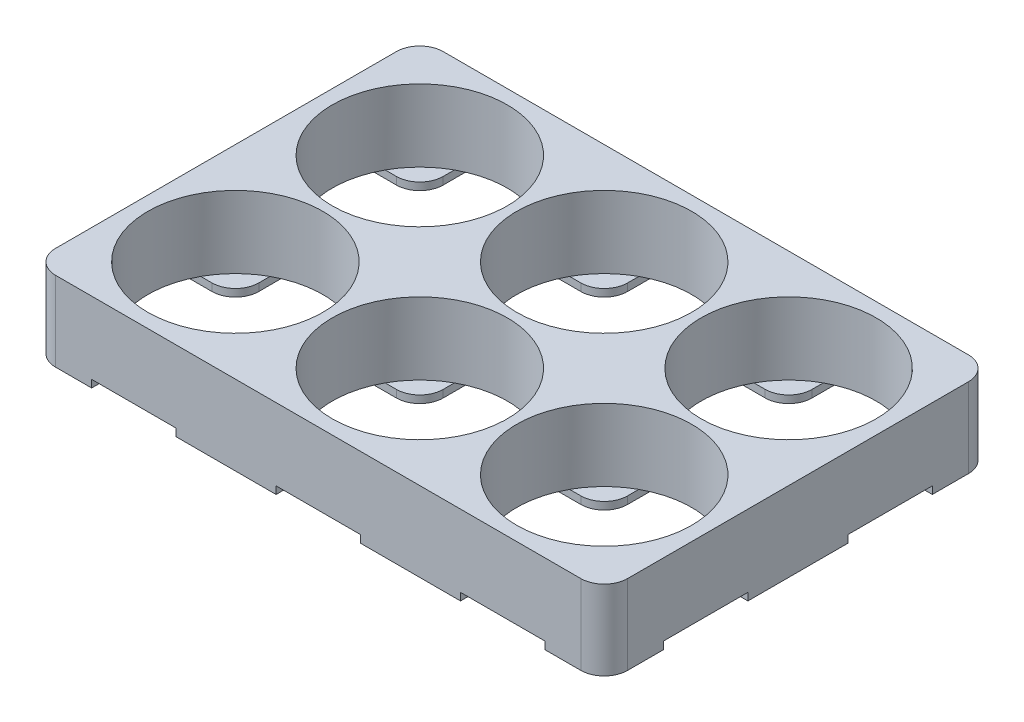
SolidWorks part; units mm, degrees
note: The reader was unsure of these and kept them because the rebuilt part matched: shared geometry of "Sketch5<3>", "Sketch12<3>".
ref_plane "Front Plane" through (0, 0, 0) normal (0, 0, 1) x (1, 0, 0)
ref_plane "Top Plane" through (0, 0, 0) normal (0, 1, 0) x (1, 0, 0)
ref_plane "Right Plane" through (0, 0, 0) normal (1, 0, 0) x (0, 0, -1)
sketch "Sketch3" plane through (0, 0, 0) normal (0, 1, 0) x (1, 0, 0)
  line L0 (-19.7, 9.85) -> (-10.35, 9.85) construction
  line L1 (-10.35, 9.85) -> (-9.35, 9.85) construction
  line L2 (-9.35, 9.85) -> (0, 9.85) construction
  line L3 (0, 9.85) -> (9.35, 9.85) construction
  line L4 (9.35, 9.85) -> (10.35, 9.85) construction
  line L5 (10.35, 9.85) -> (19.7, 9.85) construction
  line L6 (19.7, 9.85) -> (19.7, 0.5) construction
  line L7 (19.7, 0.5) -> (19.7, -0.5) construction
  line L8 (19.7, -0.5) -> (19.7, -9.85) construction
  line L9 (19.7, -9.85) -> (10.35, -9.85) construction
  line L10 (10.35, -9.85) -> (9.35, -9.85) construction
  line L11 (9.35, -9.85) -> (0, -9.85) construction
  line L12 (0, -9.85) -> (-9.35, -9.85) construction
  line L13 (-9.35, -9.85) -> (-10.35, -9.85) construction
  line L14 (-10.35, -9.85) -> (-19.7, -9.85) construction
  line L15 (-19.7, -9.85) -> (-19.7, -0.5) construction
  line L16 (-19.7, -0.5) -> (-19.7, 0.5) construction
  line L17 (-19.7, 0.5) -> (-19.7, 9.85) construction
  line L18 (0, 9.85) -> (0, 0.5) construction
  line L19 (0, 0.5) -> (0, -0.5) construction
  line L20 (0, -0.5) -> (0, -9.85) construction
  line L21 (0, 9.85) -> (0, 19.2) construction
  line L22 (-30.55, 20.7) -> (30.55, 20.7)
  line L23 (-30.55, 20.7) -> (-30.55, -20.7)
  line L24 (-30.55, -20.7) -> (30.55, -20.7)
  line L25 (30.55, 20.7) -> (30.55, -20.7)
  line L26 (0, 19.2) -> (0, 20.7) construction
  line L27 (-19.7, -9.85) -> (-29.05, -9.85) construction
  line L28 (-29.05, -9.85) -> (-30.55, -9.85) construction
  line L29 (-30.55, 20.7) -> (30.55, -20.7) construction
  circle A0 centre (-19.7, 9.85) radius 9.35
  circle A1 centre (0, 9.85) radius 9.35
  circle A2 centre (19.7, 9.85) radius 9.35
  circle A3 centre (-19.7, -9.85) radius 9.35
  circle A4 centre (0, -9.85) radius 9.35
  circle A5 centre (19.7, -9.85) radius 9.35
  dimension "D1" = 18.7
  dimension "D2" = 1
  dimension "D3" = 1
  dimension "D4" = 1
  dimension "D5" = 1.5
  dimension "D6" = 1.5
extrude "Boss-Extrude1" add sketch "Sketch3" along normal blind 66
sketch "Sketch4" plane through (0, 0, 0) normal (0, 1, 0) x (1, 0, 0)
  line L0 (-9.85, 0) -> (9.85, 0) construction
  line L1 (-19.7, -9.85) -> (0, 9.85) construction
  line L2 (-15.2615, 19.2) -> (-4.4385, 19.2)
  line L4 (-8.86, 15.2) -> (-10.84, 15.2)
  line L6 (-9.85, 19.2) -> (-9.85, 15.2) construction
  line L7 (-9.85, 0) -> (-9.85, 15.2) construction
  line L8 (-9.85, 19.2) -> (-9.85, 20.7) construction
  line L9 (30.55, 20.7) -> (-30.55, 20.7) construction
  line L10 (-9.85, 0) -> (-12.0279, 2.1779) construction
  line L11 (-12.0279, 2.1779) -> (-12.3814, 2.5314) construction
  line L12 (-12.3814, 2.5314) -> (-19.7, 9.85) construction
  line L13 (-4.4385, 19.2) -> (4.4385, 19.2) construction
  line L14 (4.4385, 19.2) -> (15.2615, 19.2)
  line L15 (15.2615, 19.2) -> (24.1385, 19.2) construction
  line L16 (24.1385, 19.2) -> (29.05, 19.2)
  line L17 (29.05, 19.2) -> (29.05, 14.2885)
  line L18 (29.05, 5.4115) -> (29.05, -5.4115)
  line L19 (29.05, -19.2) -> (29.05, -14.2885)
  line L20 (29.05, -19.2) -> (24.1385, -19.2)
  line L21 (24.1385, -19.2) -> (15.2615, -19.2) construction
  line L22 (15.2615, -19.2) -> (4.4385, -19.2)
  line L23 (4.4385, -19.2) -> (-4.4385, -19.2) construction
  line L24 (-4.4385, -19.2) -> (-15.2615, -19.2)
  line L25 (-15.2615, -19.2) -> (-24.1385, -19.2) construction
  line L26 (-24.1385, -19.2) -> (-29.05, -19.2)
  line L27 (-29.05, -19.2) -> (-29.05, -14.2885)
  line L28 (-29.05, -14.2885) -> (-29.05, -5.4115) construction
  line L29 (-29.05, -5.4115) -> (-29.05, 5.4115)
  line L30 (-29.05, 5.4115) -> (-29.05, 14.2885) construction
  line L31 (-29.05, 14.2885) -> (-29.05, 19.2)
  line L32 (-29.05, 19.2) -> (-24.1385, 19.2)
  line L33 (-24.1385, 19.2) -> (-15.2615, 19.2) construction
  line L34 (-30.55, 20.7) -> (-30.55, -20.7) construction
  line L35 (30.55, -20.7) -> (30.55, 20.7) construction
  line L36 (-30.55, -20.7) -> (30.55, -20.7) construction
  line L37 (29.05, 14.2885) -> (29.05, 5.4115) construction
  line L38 (29.05, -14.2885) -> (29.05, -5.4115) construction
  line L39 (8.86, 15.2) -> (10.84, 15.2)
  line L40 (25.05, 0.99) -> (25.05, -0.99)
  line L41 (0, -20.2) -> (19.7, -20.2)
  line L42 (10.84, -15.2) -> (8.86, -15.2)
  line L43 (-8.86, -15.2) -> (-10.84, -15.2)
  line L44 (-30.05, 9.85) -> (-30.05, -9.85)
  line L45 (-25.05, 0.99) -> (-25.05, -0.99)
  circle A0 centre (-9.85, 0) radius 3.08
  circle A1 centre (9.85, 0) radius 3.08
  circle A2 centre (-19.7, 9.85) radius 10.35
  circle A3 centre (-19.7, 9.85) radius 9.35 construction
  circle A4 centre (0, 9.85) radius 10.35
  circle A5 centre (19.7, 9.85) radius 10.35
  circle A6 centre (19.7, -9.85) radius 10.35
  circle A7 centre (0, -9.85) radius 10.35
  circle A8 centre (-19.7, -9.85) radius 10.35
  dimension "D1" = 0.5
  dimension "D2" = 1
  dimension "D3" = 4
  dimension "D4" = 1.5
  dimension "D5" = 1.5
  dimension "D6" = 1.5
  dimension "D7" = 1.5
  dimension "D8" = 4
  dimension "D9" = 4
  dimension "D10" = 4
  dimension "D11" = 4
  dimension "D12" = 4
extrude "Cut-Extrude1" cut sketch "Sketch4" along normal through all contours A0 | A1 | A4 L2 A2 L4 | A5 L14 A4 L39 | A6 L18 A5 L40 | A6 L20 L19 | A5 L17 L16 | A7 L22 A6 L42 | A8 L24 A7 L43 | A8 L27 L26 | A8 L45 A2 L29 | A2 L32 L31
sketch "Sketch5" plane through (0, 0, 0) normal (0, 0, 1) x (1, 0, 0)
  line L0 (-30.55, 66) -> (-30.55, 0) construction
  line L1 (-30.55, 57.5) -> (30.55, 57.5)
  line L2 (-30.55, 57.5) -> (-30.55, 8.5)
  line L3 (-30.55, 8.5) -> (30.55, 8.5)
  line L4 (30.55, 57.5) -> (30.55, 8.5)
  line L5 (30.55, 66) -> (30.55, 0) construction
  line L6 (0, 0) -> (0, 8.5) construction
  line L7 (0, 8.5) -> (0, 57.5) construction
  line L8 (0, 57.5) -> (0, 66) construction
  line L9 (-30.55, 66) -> (30.55, 66) construction
  line L10 (-29.05, 57.5) -> (-29.05, 8.5)
  line L11 (-30.55, 57.5) -> (30.55, 57.5)
  line L12 (-30.55, 57.5) -> (-30.55, 58.5)
  line L13 (-30.55, 58.5) -> (30.55, 58.5)
  line L14 (30.55, 57.5) -> (30.55, 58.5)
  line L15 (-30.55, 8.5) -> (30.55, 8.5)
  line L16 (-30.55, 8.5) -> (-30.55, 7.5)
  line L17 (-30.55, 7.5) -> (30.55, 7.5)
  line L18 (30.55, 8.5) -> (30.55, 7.5)
  line L19 (29.05, 57.5) -> (29.05, 8.5)
  dimension "D1" = 8.5
  dimension "D2" = 1
  dimension "D3" = 1.5
  dimension "D4" = 1.5
extrude "Boss-Extrude2" add sketch "Sketch5" along normal up to surface and the other way up to surface contours L1 L14 L13 L12 | L18 L3 L16 L17 up to face at (0, 33, 20.7) other way up to face at (0, 33, -20.7)
extrude "Cut-Extrude3" cut sketch "Sketch5<3>" against normal through all both and the other way through all contours L4 L1 L2 L3
sketch "Sketch5<3>" plane through (0, 0, 0) normal (0, 0, 1) x (1, 0, 0) same geometry as "Sketch5"
sketch "Sketch7" plane through (0, 0, 0) normal (0, 1, 0) x (1, 0, 0)
  circle A0 centre (-19.7, 9.85) radius 9.35
  circle A1 centre (0, 9.85) radius 9.35
  circle A2 centre (19.7, 9.85) radius 9.35
  circle A3 centre (19.7, -9.85) radius 9.35
  circle A4 centre (0, -9.85) radius 9.35
  circle A5 centre (-19.7, -9.85) radius 9.35
  circle A6 centre (-19.7, -9.85) radius 9.35 construction
  circle A7 centre (0, 9.85) radius 9.35 construction
  circle A8 centre (-19.7, 9.85) radius 9.35 construction
  circle A9 centre (19.7, 9.85) radius 9.35 construction
  circle A10 centre (19.7, -9.85) radius 9.35 construction
  circle A11 centre (0, -9.85) radius 9.35 construction
extrude "Cut-Extrude4" cut sketch "Sketch7" along normal through all
sketch "Sketch8" plane through (0, 0, 0) normal (0, 0, 1) x (1, 0, 0)
  line L0 (-42.55, 55.5) -> (-42.55, 10.5) construction
  line L1 (-42.55, 10.5) -> (42.55, 10.5) construction
  line L2 (42.55, 10.5) -> (42.55, 55.5) construction
  line L3 (42.55, 55.5) -> (-42.55, 55.5) construction
  line L4 (0, 55.5) -> (0, 10.5) construction
  line L5 (-29.05, 8.5) -> (29.05, 57.5) construction
  line L6 (-42.55, 63.5) -> (-30.55, 63.5)
  line L7 (-30.55, 66) -> (-30.55, 0) construction
  line L8 (-30.55, 63.5) -> (-30.55, 47.5)
  line L9 (-30.55, 47.5) -> (-42.55, 47.5)
  line L10 (-42.55, 18.5) -> (-30.55, 18.5)
  line L11 (-42.55, 2.5) -> (-30.55, 2.5)
  line L12 (-30.55, 2.5) -> (-30.55, 18.5)
  line L13 (42.55, 2.5) -> (30.55, 2.5)
  line L14 (30.55, 66) -> (30.55, 0) construction
  line L15 (42.55, 18.5) -> (30.55, 18.5)
  line L16 (30.55, 18.5) -> (30.55, 2.5)
  line L17 (42.55, 47.5) -> (30.55, 47.5)
  line L18 (42.55, 63.5) -> (30.55, 63.5)
  line L19 (30.55, 63.5) -> (30.55, 47.5)
  line L20 (50.55, 55.5) -> (50.55, 10.5) construction
  line L21 (50.55, 33) -> (30.55, 33) construction
  circle A0 centre (-42.55, 55.5) radius 5.5
  circle A1 centre (-42.55, 10.5) radius 5.5
  circle A2 centre (42.55, 10.5) radius 5.5
  circle A3 centre (42.55, 55.5) radius 5.5
  circle A4 centre (-42.55, 55.5) radius 8
  circle A5 centre (-42.55, 10.5) radius 8
  circle A6 centre (42.55, 10.5) radius 8
  circle A7 centre (42.55, 55.5) radius 8
  point P14 (0, 33)
  dimension "D1" = 2.5
  dimension "D2" = 16
  dimension "D3" = 45
  dimension "D4" = 20
extrude "Boss-Extrude3" add sketch "Sketch8" along normal up to surface and the other way up to surface contours A4 L9 L8 L6 | A4 A0 | A7 L18 L19 L17 | A7 A3 | A6 L15 L16 L13 | A6 A2 | A5 A1 | A5 L11 L12 L10
sketch "Sketch9" plane through (0, 0, 0) normal (0, 1, 0) x (1, 0, 0)
  line L0 (-30.55, 20.7) -> (-50.55, 20.7)
  line L1 (-50.55, 20.7) -> (-50.55, 5.7)
  line L2 (-50.55, 20.7) -> (-50.55, -20.7) construction
  line L3 (-50.55, 5.7) -> (-46.55, 5.7)
  line L4 (-46.55, 5.7) -> (-30.55, -4.3)
  line L5 (-30.55, -20.7) -> (-30.55, 20.7) construction
  line L6 (-30.55, -4.3) -> (-30.55, 20.7)
  line L7 (-30.55, -4.3) -> (30.55, -4.3) construction
  line L8 (30.55, -20.7) -> (30.55, 20.7) construction
  line L9 (30.55, -4.3) -> (30.55, 20.7)
  line L10 (30.55, 20.7) -> (42.55, 20.7) construction
  line L11 (30.55, -4.3) -> (46.55, 5.7)
  line L12 (46.55, 5.7) -> (50.55, 5.7)
  line L13 (50.55, -20.7) -> (50.55, 20.7) construction
  line L14 (50.55, 5.7) -> (50.55, 20.7)
  line L15 (50.55, 20.7) -> (30.55, 20.7)
  line L16 (-50.55, 5.7) -> (-50.55, -20.7)
  line L17 (-50.55, -20.7) -> (-30.55, -20.7)
  line L18 (-30.55, -20.7) -> (-30.55, -4.3)
  line L19 (50.55, 5.7) -> (50.55, -20.7)
  line L20 (50.55, -20.7) -> (30.55, -20.7)
  line L21 (30.55, -20.7) -> (30.55, -4.3)
  dimension "D1" = 4
  dimension "D2" = 15
  dimension "D3" = 25
extrude "Cut-Extrude6" cut sketch "Sketch9" against normal through all and the other way through all contours L17 L18 L4 L3 L16 | L21 L20 L19 L12 L11
sketch "Sketch10" plane through (0, 0, -20.7) normal (0, 0, -1) x (-1, 0, 0)
  circle A0 centre (42.55, 10.5) radius 2.25
  circle A1 centre (42.55, 10.5) radius 8
  circle A2 centre (42.55, 55.5) radius 2.25
  circle A3 centre (42.55, 55.5) radius 8
  circle A4 centre (-42.55, 55.5) radius 8
  circle A5 centre (-42.55, 55.5) radius 2.25
  circle A6 centre (-42.55, 10.5) radius 2.25
  circle A7 centre (-42.55, 10.5) radius 8
  arc A8 (-42.55, 18.5) -> (-42.55, 2.5) centre (-42.55, 10.5) ccw construction
  arc A9 (42.55, 2.5) -> (42.55, 18.5) centre (42.55, 10.5) ccw construction
  arc A10 (42.55, 47.5) -> (42.55, 63.5) centre (42.55, 55.5) ccw construction
  arc A11 (-42.55, 63.5) -> (-42.55, 47.5) centre (-42.55, 55.5) ccw construction
  dimension "D1" = 4.5
extrude "Boss-Extrude4" add sketch "Sketch10" against normal blind 5
sketch "Sketch11" plane through (0, 66, 0) normal (0, 1, 0) x (1, 0, 0)
  line L1 (-30.55, 20.7) -> (30.55, 20.7)
  line L2 (-30.55, 20.7) -> (-30.55, -20.7)
  line L3 (-30.55, -20.7) -> (30.55, -20.7)
  line L4 (30.55, 20.7) -> (30.55, -20.7)
  line L5 (-29.05, 19.2) -> (29.05, 19.2)
  line L6 (-29.05, 19.2) -> (-29.05, -19.2)
  line L7 (-29.05, -19.2) -> (29.05, -19.2)
  line L8 (29.05, 19.2) -> (29.05, -19.2)
extrude "Boss-Extrude5" add sketch "Sketch11" along normal blind 4
sketch "Sketch12" plane through (0, 66, 0) normal (0, 1, 0) x (1, 0, 0)
  line L0 (-24.2, -14.35) -> (24.2, -14.35)
  line L9 (24.2, -14.35) -> (24.2, 14.35)
  line L10 (24.2, 14.35) -> (-24.2, 14.35)
  line L11 (-24.2, 14.35) -> (-24.2, -14.35)
  line L12 (-15.2, -5.35) -> (-4.5, -5.35)
  line L13 (-4.5, -5.35) -> (-4.5, 5.35)
  line L14 (-4.5, 5.35) -> (-15.2, 5.35)
  line L15 (-15.2, 5.35) -> (-15.2, -5.35)
  line L16 (15.2, -5.35) -> (4.5, -5.35)
  line L17 (4.5, -5.35) -> (4.5, 5.35)
  line L18 (4.5, 5.35) -> (15.2, 5.35)
  line L19 (15.2, 5.35) -> (15.2, -5.35)
  line L20 (4.5, -5.35) -> (-4.5, -5.35) construction
  line L21 (4.5, 5.35) -> (-4.5, 5.35) construction
  line L22 (0, 0) -> (0, -5.35) construction
  line L23 (0, 0) -> (-4.5, 0) construction
  line L24 (24.2, 0) -> (15.2, 0)
  line L25 (-9.85, -5.35) -> (-9.85, -14.35) construction
  line L26 (-9.85, -9.85) -> (-19.7, -9.85) construction
  line L27 (-15.2, 0) -> (-24.2, 0) construction
  line L28 (-19.7, -9.85) -> (-19.7, 0) construction
  arc M21 (-29.05, -9.85) -> (-19.7, -19.2) centre (-19.7, -9.85) cw
  circle M27 centre (0, -9.85) radius 9.35
  arc M33 (19.7, -19.2) -> (29.05, -9.85) centre (19.7, -9.85) cw
  arc M39 (29.05, 9.85) -> (19.7, 19.2) centre (19.7, 9.85) cw
  circle M45 centre (0, 9.85) radius 9.35
  arc M51 (-19.7, 19.2) -> (-29.05, 9.85) centre (-19.7, 9.85) cw
  dimension "D1" = 9
  dimension "D2" = 9
  dimension "D3" = 9
  dimension "D4" = 9
extrude "Cut-Extrude7" cut sketch "Sketch12" against normal blind 0.8 contours L15 L14 L10 L11 M51 | L15 L11 L0 L12 M21 | L12 L0 M21 M27 | L16 L17 L13 L12 L0 M27 | L17 L18 L10 L14 L13 M45 | L14 L10 M45 M51 | L17 L13 M27 M45 | L19 L16 L0 L9 M33 | L18 L19 L9 L10 M39 | L24 L9 L19 M39 | L9 L24 L19 M33 | L16 L0 M33 M27 | L18 L10 M45 M39 | L15 L11 M51 M21
extrude "Cut-Extrude8" cut sketch "Sketch12<3>" along normal blind 0.8 from surface at -66 contours L15 L14 L10 L11 M51 | L15 L11 L0 L12 M21 | L15 L11 M51 M21 | L12 L0 M21 M27 | L14 L10 M45 M51 | L17 L18 L10 L14 L13 M45 | L16 L17 L13 L12 L0 M27 | L17 L13 M27 M45 | L19 L16 L0 L9 M33 | L18 L19 L9 L10 M39 | L18 L10 M45 M39 | L16 L0 M33 M27 | L9 L24 L19 M33 | L24 L9 L19 M39 starting at face at (9.85, 0, 3.08)
sketch "Sketch12<3>" plane through (0, 66, 0) normal (0, 1, 0) x (1, 0, 0) same geometry as "Sketch12"
sketch "Sketch13" plane through (0, 0, 0) normal (0, 0, 1) x (1, 0, 0)
  line L1 (-50.55, 70) -> (50.55, 70)
  line L2 (-50.55, 70) -> (-50.55, 8.5)
  line L3 (-50.55, 8.5) -> (50.55, 8.5)
  line L4 (50.55, 70) -> (50.55, 8.5)
  line L9 (-30.55, 70) -> (30.55, 70) construction
  line L10 (9.35, 8.5) -> (-9.35, 8.5) construction
  line L12 (-50.55, 8.5) -> (-50.55, 0)
  line L13 (-50.55, 0) -> (-30.55, 0)
  line L14 (-30.55, 0) -> (-30.55, 8.5)
  line L15 (-30.55, 70) -> (-30.55, 0) construction
  line L16 (50.55, 8.5) -> (50.55, 0)
  line L17 (50.55, 0) -> (30.55, 0)
  line L18 (30.55, 0) -> (30.55, 8.5)
  line L19 (30.55, 70) -> (30.55, 0) construction
  arc A0 (-46.55, 62.4282) -> (-46.55, 48.5718) centre (-42.55, 55.5) ccw construction
  arc A1 (46.55, 48.5718) -> (46.55, 62.4282) centre (42.55, 55.5) ccw construction
extrude "Cut-Extrude9" cut sketch "Sketch13" against normal through all both and the other way through all contours L4 L1 L2 L3 | L13 L14 L3 L12 | L18 L17 L16 L3
sketch "Sketch14" plane through (0, 0, 0) normal (0, -1, 0) x (1, 0, 0)
  line L0 (-30.55, 20.7) -> (30.55, 20.7) construction
  line L1 (30.55, -20.7) -> (-30.55, -20.7)
  line L2 (30.55, -20.7) -> (30.55, 20.7)
  line L3 (30.55, 20.7) -> (-30.55, 20.7)
  line L4 (-30.55, -20.7) -> (-30.55, 20.7)
  line L5 (30.55, 5.35) -> (-30.55, 5.35)
  line L6 (30.55, 5.35) -> (30.55, 14.35)
  line L7 (30.55, 14.35) -> (-30.55, 14.35)
  line L8 (-30.55, 5.35) -> (-30.55, 14.35)
  line L9 (30.55, -14.35) -> (-30.55, -14.35)
  line L10 (30.55, -14.35) -> (30.55, -5.35)
  line L11 (30.55, -5.35) -> (-30.55, -5.35)
  line L12 (-30.55, -14.35) -> (-30.55, -5.35)
  line L13 (24.2, -20.7) -> (15.2, -20.7)
  line L14 (24.2, -20.7) -> (24.2, 20.7)
  line L15 (24.2, 20.7) -> (15.2, 20.7)
  line L16 (15.2, -20.7) -> (15.2, 20.7)
  line L17 (4.5, 20.7) -> (-4.5, 20.7)
  line L18 (4.5, 20.7) -> (4.5, -20.7)
  line L19 (4.5, -20.7) -> (-4.5, -20.7)
  line L20 (-4.5, 20.7) -> (-4.5, -20.7)
  line L21 (-15.2, -20.7) -> (-24.2, -20.7)
  line L22 (-15.2, -20.7) -> (-15.2, 20.7)
  line L23 (-15.2, 20.7) -> (-24.2, 20.7)
  line L24 (-24.2, -20.7) -> (-24.2, 20.7)
  line L25 (30.55, -20.7) -> (-30.55, -20.7) construction
  line L26 (-30.55, -20.7) -> (-30.55, 20.7) construction
  line L27 (-8.1959, 5.35) -> (-11.5041, 5.35) construction
  line L28 (-8.1959, 14.35) -> (-11.5041, 14.35) construction
  line L29 (-8.1959, -14.35) -> (-11.5041, -14.35) construction
  line L30 (-8.1959, -5.35) -> (-11.5041, -5.35) construction
  line L32 (24.2, 1.6541) -> (24.2, -1.6541) construction
  line L33 (15.2, 1.6541) -> (15.2, -1.6541) construction
  line L34 (4.5, 1.6541) -> (4.5, -1.6541) construction
  line L35 (-4.5, -1.6541) -> (-4.5, 1.6541) construction
  line L36 (-15.2, 1.6541) -> (-15.2, -1.6541) construction
  line L37 (-24.2, 1.6541) -> (-24.2, -1.6541) construction
  point P26 (5.1684, 20.7)
  point P29 (-14.0523, 20.7)
  point P30 (15.3184, -20.7)
  point P31 (-6.9909, -20.7)
  point P34 (-26.2393, -20.7)
  point P35 (30.55, -14.8649)
  point P36 (30.55, 6.2671)
  point P37 (-30.55, -7.084)
  point P40 (-30.55, 5.0807)
extrude "Cut-Extrude10" cut sketch "Sketch14" against normal up to surface (0.8 mm away) contours L14 L9 L2 L11 | L16 L9 L14 L11 | L11 L18 L9 L16 | L11 L20 L9 L18 | L22 L9 L20 L11 | L24 L9 L22 L11 | L9 L24 L11 L4 | L5 L24 L7 L4 | L24 L5 L22 L7 | L22 L5 L20 L7 | L7 L20 L5 L18 | L7 L18 L5 L16 | L16 L5 L14 L7 | L14 L5 L2 L7 | L16 L11 L14 L5 | L5 L20 L11 L18 | L24 L11 L22 L5 | L24 L7 L22 L3 | L16 L7 L14 L3 | L3 L20 L7 L18 | L16 L1 L14 L9 | L9 L20 L1 L18 | L24 L1 L22 L9 up to face at (-9.85, 0.8, 9.85)
sketch "Sketch16" plane through (0, 0, 0) normal (0, -1, 0) x (1, 0, 0)
  line L0 (-24.2, 19.2) -> (-24.2, 20.7) construction
  line L1 (15.2, -5.35) -> (4.5, -5.35)
  line L2 (15.2, -5.35) -> (15.2, 5.35)
  line L3 (15.2, 5.35) -> (4.5, 5.35)
  line L4 (4.5, -5.35) -> (4.5, 5.35)
  line L5 (-4.5, 5.35) -> (-15.2, 5.35)
  line L6 (-4.5, 5.35) -> (-4.5, -5.35)
  line L7 (-4.5, -5.35) -> (-15.2, -5.35)
  line L8 (-15.2, 5.35) -> (-15.2, -5.35)
  line L9 (-30.55, 20.7) -> (-24.2, 20.7)
  line L10 (-30.55, 20.7) -> (-30.55, 14.35)
  line L11 (-30.55, 14.35) -> (-24.2, 14.35)
  line L12 (-24.2, 20.7) -> (-24.2, 14.35)
  line L13 (-24.2, 5.35) -> (-30.55, 5.35)
  line L14 (-24.2, 5.35) -> (-24.2, -5.35)
  line L15 (-24.2, -5.35) -> (-30.55, -5.35)
  line L16 (-30.55, 5.35) -> (-30.55, -5.35)
  line L17 (-30.55, -20.7) -> (-24.2, -20.7)
  line L18 (-30.55, -20.7) -> (-30.55, -14.35)
  line L19 (-30.55, -14.35) -> (-24.2, -14.35)
  line L20 (-24.2, -20.7) -> (-24.2, -14.35)
  line L21 (-15.2, -14.35) -> (-4.5, -14.35)
  line L22 (-15.2, -14.35) -> (-15.2, -20.7)
  line L23 (-15.2, -20.7) -> (-4.5, -20.7)
  line L24 (-4.5, -14.35) -> (-4.5, -20.7)
  line L25 (4.5, -20.7) -> (15.2, -20.7)
  line L26 (4.5, -20.7) -> (4.5, -14.35)
  line L27 (4.5, -14.35) -> (15.2, -14.35)
  line L28 (15.2, -20.7) -> (15.2, -14.35)
  line L29 (30.55, -20.7) -> (24.2, -20.7)
  line L30 (30.55, -20.7) -> (30.55, -14.35)
  line L31 (30.55, -14.35) -> (24.2, -14.35)
  line L32 (24.2, -20.7) -> (24.2, -14.35)
  line L33 (30.55, -5.35) -> (24.2, -5.35)
  line L34 (30.55, -5.35) -> (30.55, 5.35)
  line L35 (30.55, 5.35) -> (24.2, 5.35)
  line L36 (24.2, -5.35) -> (24.2, 5.35)
  line L37 (30.55, 14.35) -> (24.2, 14.35)
  line L38 (30.55, 14.35) -> (30.55, 20.7)
  line L39 (30.55, 20.7) -> (24.2, 20.7)
  line L40 (24.2, 14.35) -> (24.2, 20.7)
  line L41 (15.2, 20.7) -> (4.5, 20.7)
  line L42 (15.2, 20.7) -> (15.2, 14.35)
  line L43 (15.2, 14.35) -> (4.5, 14.35)
  line L44 (4.5, 20.7) -> (4.5, 14.35)
  line L45 (-4.5, 20.7) -> (-15.2, 20.7)
  line L46 (-4.5, 20.7) -> (-4.5, 14.35)
  line L47 (-4.5, 14.35) -> (-15.2, 14.35)
  line L48 (-15.2, 20.7) -> (-15.2, 14.35)
  line L49 (-24.2, 19.2) -> (-24.2, 20.7) construction
  line L50 (-30.55, 5.35) -> (-30.55, 14.35) construction
  line L51 (30.55, -14.35) -> (30.55, -5.35) construction
  line L52 (15.2, -20.7) -> (15.2, -19.2) construction
  line L53 (15.2, -20.7) -> (15.2, -19.2) construction
  line L54 (30.55, 14.35) -> (29.05, 14.35) construction
  line L55 (30.55, 14.35) -> (29.05, 14.35) construction
  circle A0 centre (19.7, -9.85) radius 10.35
  circle A1 centre (19.7, 9.85) radius 10.35
  circle A2 centre (0, 9.85) radius 10.35
  circle A3 centre (-19.7, 9.85) radius 10.35
  circle A4 centre (-19.7, -9.85) radius 10.35
  circle A5 centre (0, -9.85) radius 10.35
  arc A8 (29.0205, -5.35) -> (25.05, -0.99) centre (19.7, -9.85) ccw construction
  arc A9 (4.4385, -19.2) -> (8.86, -15.2) centre (0, -9.85) ccw construction
  arc A10 (-15.2615, -19.2) -> (-10.84, -15.2) centre (-19.7, -9.85) ccw construction
  arc A11 (25.05, 0.99) -> (29.0205, 5.35) centre (19.7, 9.85) ccw construction
  arc A12 (-29.0205, 5.35) -> (-25.05, 0.99) centre (-19.7, 9.85) ccw construction
  arc A13 (-4.4385, 19.2) -> (-8.86, 15.2) centre (0, 9.85) ccw construction
extrude "Boss-Extrude6" add sketch "Sketch16" against normal up to surface (0.8 mm away) contours L32 A0 L31 | L27 A0 L28 | L33 A0 L36 | L2 A0 L1 | L1 A5 L4 | L6 A5 L7 | L26 A5 L27 | L21 A5 L24 | L22 A4 L21 | L19 A4 L20 | L14 A4 L15 | L7 A4 L8 | L36 A1 L35 | L3 A1 L2 | L4 A2 L3 | L5 A2 L6 | L8 A3 L5 | L13 A3 L14 | L12 A3 L11 | L47 A3 L48 | L46 A2 L47 | L43 A2 L44 | L42 A1 L43 | L37 A1 L40 up to face at (29.2287, 0.8, 9.85)
fillet "Fillet1" radius 2.5 32 edges at (-30.55, 4.25, -20.7) (-30.55, 4.25, 20.7) (30.55, 4.25, 20.7) (30.55, 4.25, -20.7) (24.2, 0.4, 14.35) (15.2, 0.4, 14.35) (4.5, 0.4, 14.35) (-4.5, 0.4, 14.35) (-15.2, 0.4, 14.35) (-24.2, 0.4, 14.35) (24.2, 0.4, -5.35) (15.2, 0.4, -5.35) (4.5, 0.4, -5.35) (-4.5, 0.4, -5.35) (-15.2, 0.4, -5.35) (-24.2, 0.4, -5.35) (4.5, 0.4, 5.35) (-4.5, 0.4, 5.35) (-15.2, 0.4, 5.35) (-24.2, 0.4, 5.35) (15.2, 0.4, 5.35) (24.2, 0.4, 5.35) (4.5, 0.4, -14.35) (-15.2, 0.4, -14.35) (-24.2, 0.4, -14.35) (-4.5, 0.4, -14.35) (15.2, 0.4, -14.35) (24.2, 0.4, -14.35) (-29.05, 3.75, -19.2) (-29.05, 3.75, 19.2) (29.05, 3.75, 19.2) (29.05, 3.75, -19.2)
